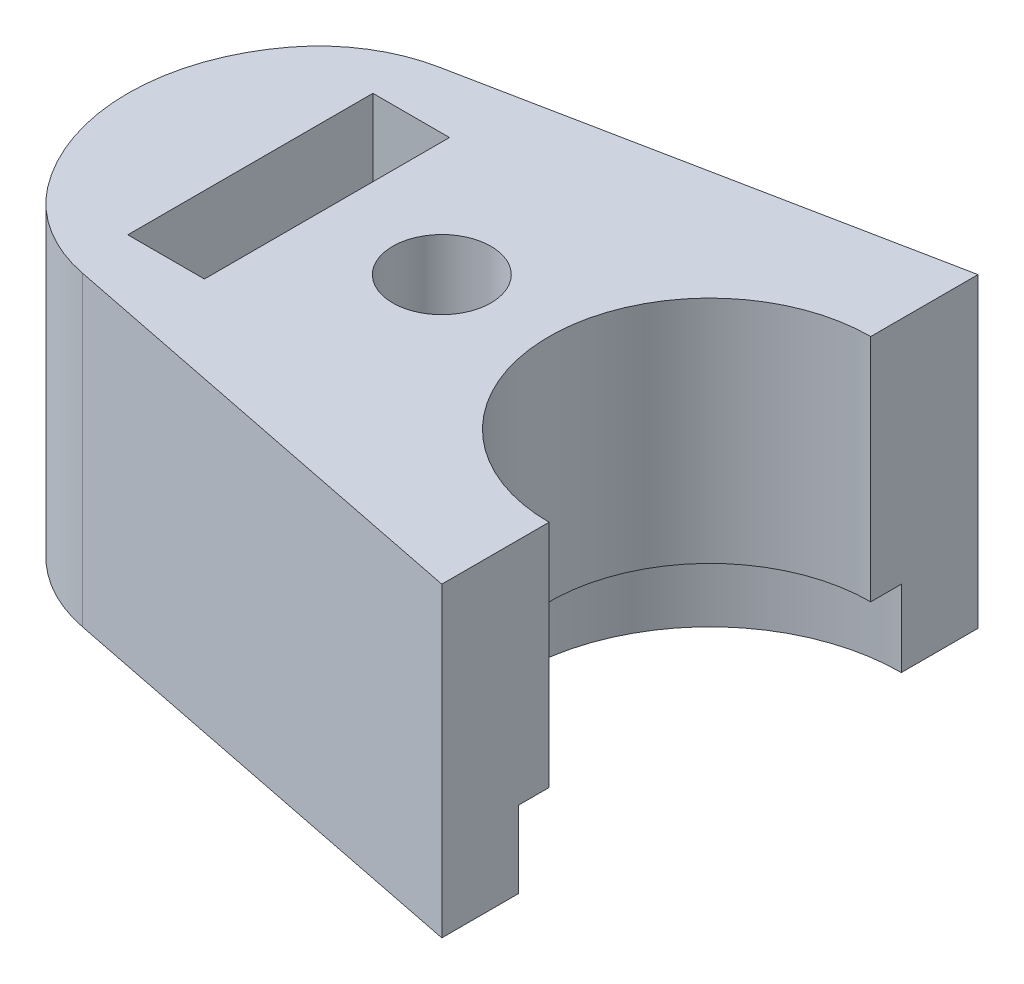
SolidWorks part; units mm, degrees
ref_plane "Front Plane" through (0, 0, 0) normal (0, 0, 1) x (1, 0, 0)
ref_plane "Top Plane" through (0, 0, 0) normal (0, 1, 0) x (1, 0, 0)
ref_plane "Right Plane" through (0, 0, 0) normal (1, 0, 0) x (0, 0, -1)
sketch "Sketch1" plane through (0, 0, 0) normal (0, 1, 0) x (1, 0, 0)
  line L0 (-0.1139, 1.9772) -> (-1.25, 1.7502)
  line L1 (-0.1139, -1.9772) -> (-1.25, -1.7502)
  line L2 (-1.25, 1.25) -> (-1.25, 1.7502)
  line L3 (-1.25, -1.25) -> (-1.25, -1.7502)
  line L4 (-1.25, -1.7502) -> (-4.1832, -1.1642)
  line L5 (-1.25, 1.7502) -> (-4.1832, 1.1642)
  line L6 (-1.25, 1.25) -> (-1.25, 1.05)
  line L7 (-1.25, -1.25) -> (-1.25, -1.05)
  line L8 (0, 1.6) -> (0, 1.3)
  line L9 (0, -1.3) -> (0, -1.6)
  line L17 (-4.25, 0.8) -> (-3.75, 0.8)
  line L18 (-4.25, 0.8) -> (-4.25, -0.8)
  line L19 (-4.25, -0.8) -> (-3.75, -0.8)
  line L20 (-3.75, 0.8) -> (-3.75, -0.8)
  circle A0 centre (-1.25, 0) radius 1.25
  circle A1 centre (-1.25, 0) radius 1.05
  arc A2 (0.1641, 1.9933) -> (0.1641, -1.9933) centre (0, 0) cw
  arc A3 (-0.1139, -1.9772) -> (0.1641, -1.9933) centre (0.0821, -0.9966) ccw
  arc A4 (-4.7783, 0.7954) -> (-4.7783, -0.7954) centre (-3.75, 0) ccw
  arc A5 (0.1641, 1.9933) -> (-0.1139, 1.9772) centre (0.0821, 0.9966) ccw
  arc A6 (-4.1832, 1.1642) -> (-4.7783, 0.7954) centre (-3.9873, 0.1835) ccw
  arc A7 (-4.1832, -1.1642) -> (-4.7783, -0.7954) centre (-3.9873, -0.1835) cw
  circle A8 centre (-3, 0) radius 0.3207
  circle A9 centre (0.5, 0) radius 0.3207
  arc A10 (0, 1.6) -> (0, -1.6) centre (0, 0) cw
  arc A11 (0, 1.3) -> (0, -1.3) centre (0, 0) cw
  point P12 (-3, 0)
  point P20 (0.5, 0)
extrude "Boss-Extrude1" add sketch "Sketch1" along normal blind 0.5 contours A7 L4 L3 A0 L2 L5 A6 A4 A8 L17 L20 L19 L18 region at (-1.3017, 0, -1.5001)
extrude "Boss-Extrude2" add sketch "Sketch1<20>" along normal blind 1.5 from offset 0.5 contours A1 L6 A0 L7 | A7 L4 L3 A0 L2 L5 A6 A4 A8 L17 L20 L19 L18 region at (-1.3017, 0, -1.5001) region at (-1.278, 0, -1.15)
sketch "Sketch1<20>" plane through (0, 0, 0) normal (0, 1, 0) x (1, 0, 0) same geometry as "Sketch1"
